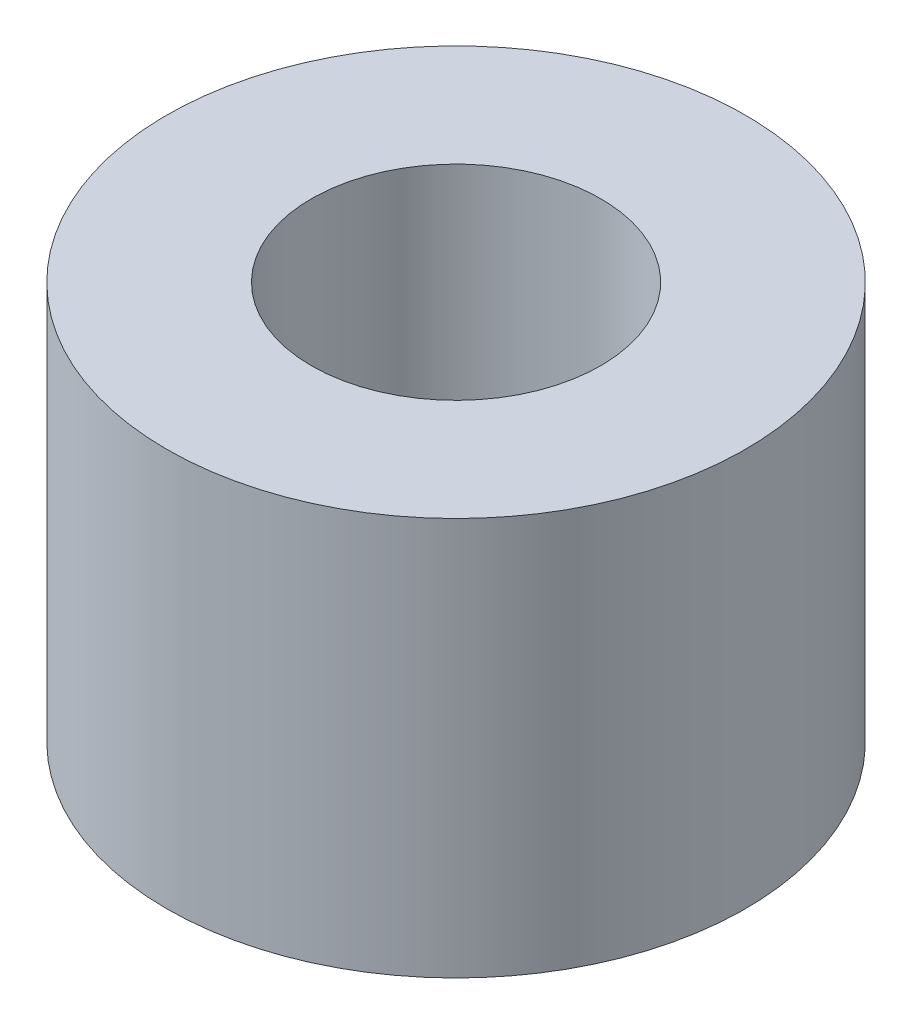
SolidWorks part; units mm, degrees
ref_plane "Front Plane" through (0, 0, 0) normal (0, 0, 1) x (1, 0, 0)
ref_plane "Top Plane" through (0, 0, 0) normal (0, 1, 0) x (1, 0, 0)
ref_plane "Right Plane" through (0, 0, 0) normal (1, 0, 0) x (0, 0, -1)
sketch "Sketch1" plane through (0, 0, 0) normal (0, 1, 0) x (1, 0, 0)
  circle A0 centre (0, 0) radius 2
  circle A1 centre (0, 0) radius 4
  dimension "D1" = 4
  dimension "D2" = 8
extrude "Boss-Extrude1" add sketch "Sketch1" along normal blind 5.5
